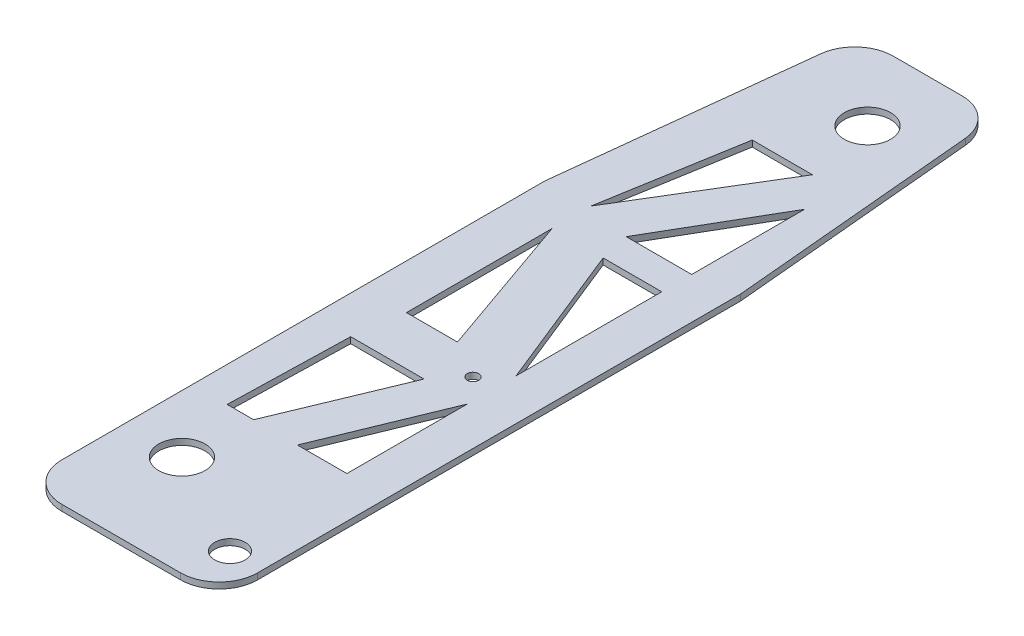
SolidWorks part; units mm, degrees
ref_plane "Front" through (0, 0, 0) normal (0, 0, 1) x (1, 0, 0)
ref_plane "Top" through (0, 0, 0) normal (0, 1, 0) x (1, 0, 0)
ref_plane "Right" through (0, 0, 0) normal (1, 0, 0) x (0, 0, -1)
sketch "Sketch1" plane through (0, 0, 0) normal (0, 1, 0) x (1, 0, 0)
  line L0 (10.4543, 228.6) -> (0, 135.3627)
  line L1 (0, 0) -> (50.8, 0)
  line L2 (0, 0) -> (0, 228.6)
  line L3 (0, 228.6) -> (50.8, 228.6)
  line L4 (50.8, 0) -> (50.8, 228.6)
  line L5 (42.3273, 228.6) -> (50.8, 135.3627)
  line L8 (50.8, 0) -> (24.327, 0)
  line L9 (50.8, 0) -> (50.8, -15)
  line L10 (50.8, -15) -> (24.327, -15)
  line L11 (24.327, 0) -> (24.327, -15)
  circle A0 centre (29.5042, 189.5572) radius 6
  circle A2 centre (24.327, 25.5092) radius 5.969
  circle A3 centre (42.3273, 11.2956) radius 3.9601
  dimension "D3" = 12
  dimension "D4" = 11.938
  dimension "D5" = 15
  dimension "D1" = 50.8
  dimension "D2" = 228.6
extrude "Boss-Extrude1" add sketch "Sketch1" along normal blind 1.5875 contours L1 L4 L3 L0 L2 region at (25.456, 0, -107.8992)
sketch "Sketch2" plane through (0, 1.5875, 0) normal (0, 1, 0) x (1, 0, 0)
  line L0 (17.7103, 171.4473) -> (11.6259, 135.6828)
  line L3 (17.7103, 171.4473) -> (33.327, 171.4473)
  line L4 (33.327, 171.4473) -> (11.6259, 135.6828)
  line L5 (40.07, 162.6734) -> (40.07, 137.6523)
  line L8 (40.07, 162.6734) -> (23.0737, 133.3724)
  line L9 (23.0737, 133.3724) -> (40.07, 133.3724)
  line L10 (40.07, 133.3724) -> (40.07, 137.6523)
  line L11 (11.6259, 125.5961) -> (11.6259, 87.7975)
  line L12 (11.6259, 87.7975) -> (24.8595, 87.7975)
  line L13 (24.8595, 87.7975) -> (11.6259, 125.5961)
  line L14 (24.8595, 125.5961) -> (40.07, 125.5961)
  line L15 (40.07, 125.5961) -> (40.07, 87.7975)
  line L16 (40.07, 87.7975) -> (24.8595, 125.5961)
  line L20 (28.8434, 75.1474) -> (9.809, 75.1474)
  line L23 (40.07, 75.1474) -> (40.07, 43.8914)
  line L24 (40.07, 43.8914) -> (31.2784, 43.8914)
  line L26 (40.07, 75.1474) -> (27.2385, 43.8914)
  line L27 (27.2385, 43.8914) -> (31.2784, 43.8914)
  line L28 (9.809, 75.1474) -> (9.002, 43.8914)
  line L30 (28.8434, 75.1474) -> (15.8732, 43.8914)
  line L31 (15.8732, 43.8914) -> (9.002, 43.8914)
extrude "Cut-Extrude1" cut sketch "Sketch2" against normal blind 10
sketch "Sketch4" plane through (0, 0, -228.6) normal (0, 0, -1) x (-1, 0, 0)
  line L1 (-61.3109, 11.9192) -> (4.9615, 11.9192)
  line L2 (-61.3109, 11.9192) -> (-61.3109, -15.8811)
  line L3 (-61.3109, -15.8811) -> (4.9615, -15.8811)
  line L4 (4.9615, 11.9192) -> (4.9615, -15.8811)
extrude "Cut-Extrude2" cut sketch "Sketch4" against normal blind 20
sketch "Sketch5" plane through (0, 0, 0) normal (0, -1, 0) x (1, 0, 0)
  circle A0 centre (24.327, -25.5092) radius 6.6837
extrude "Boss-Extrude2" add sketch "Sketch5" against normal blind 1.5875
sketch "Sketch6" plane through (0, 0, 0) normal (0, -1, 0) x (1, 0, 0)
  line L0 (0, 0) -> (0, -135.3627) construction
  circle A0 centre (15, -26.1497) radius 6
  circle A1 centre (29.5042, -189.5572) radius 6 construction
  dimension "D1" = 164.05
  dimension "D2" = 12
  dimension "D3" = 15
extrude "Cut-Extrude3" cut sketch "Sketch6" against normal blind 2
fillet "Fillet3" radius 10 1 edges at (44.1447, 0.7937, -208.6)
sketch "Sketch7" plane through (0, 0, 0) normal (0, -1, 0) x (1, 0, 0)
  circle A0 centre (34.714, -81.9581) radius 1.5
extrude "Cut-Extrude4" cut sketch "Sketch7" against normal blind 3.175
fillet "Fillet4" radius 10 3 edges at (50.8, 0.7937, 0) (0, 0.7937, 0) (8.2118, 0.7937, -208.6)
equation "\"7i\"=101.6"
